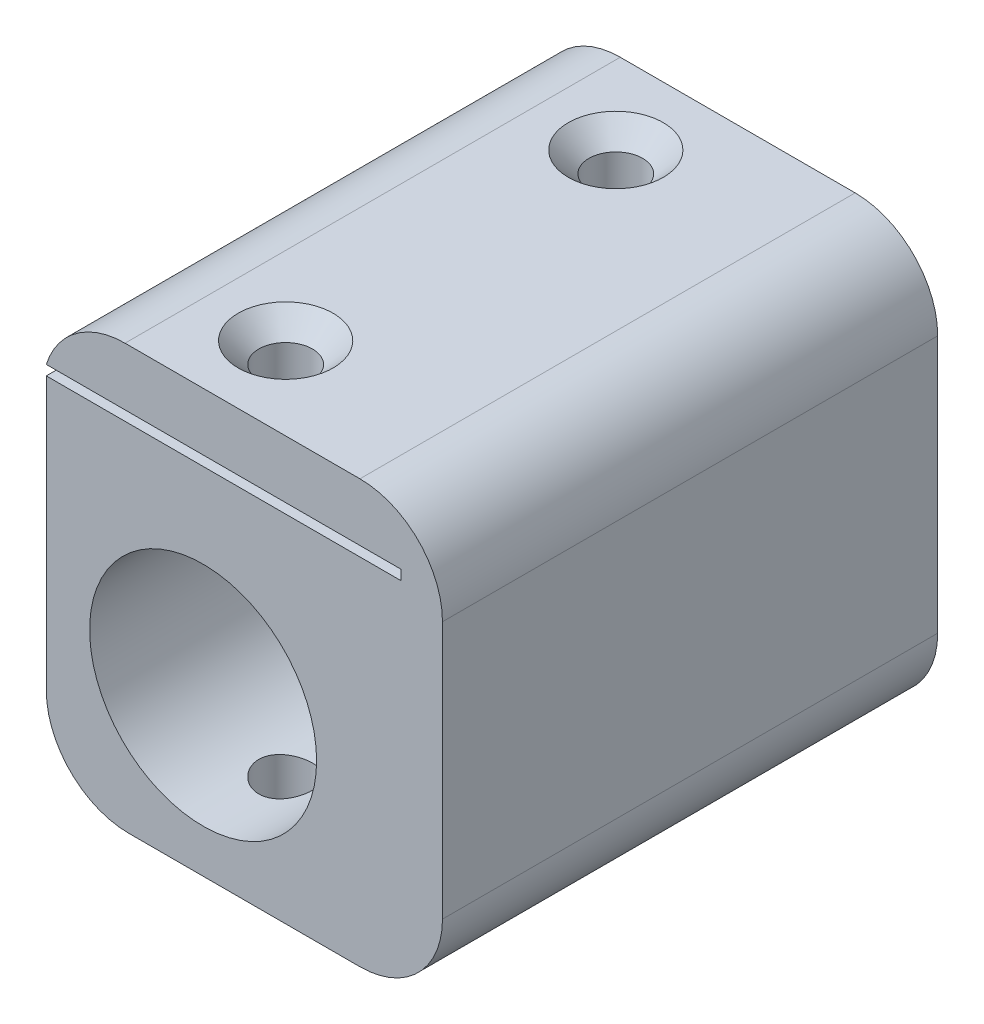
SolidWorks part; units mm, degrees
ref_plane "Front Plane" through (0, 0, 0) normal (0, 0, 1) x (1, 0, 0)
ref_plane "Top Plane" through (0, 0, 0) normal (0, 1, 0) x (1, 0, 0)
ref_plane "Right Plane" through (0, 0, 0) normal (1, 0, 0) x (0, 0, -1)
sketch "Sketch1" plane through (0, 0, 0) normal (0, 0, 1) x (1, 0, 0)
  line L1 (-19, -19) -> (24, -19)
  line L2 (-19, -19) -> (-19, 24)
  line L3 (-19, 24) -> (24, 24)
  line L4 (24, -19) -> (24, 24)
  line L7 (24, -19) -> (29, -19)
  line L8 (24, -19) -> (24, 32.2)
  line L9 (24, 32.2) -> (29, 32.2)
  line L10 (29, -19) -> (29, 32.2)
  line L11 (24, 32.2) -> (-19, 32.2)
  line L12 (24, 32.2) -> (24, 25.2)
  line L13 (24, 25.2) -> (-19, 25.2)
  line L14 (-19, 32.2) -> (-19, 25.2)
  circle A0 centre (0, 0) radius 13.75
  dimension "D1" = 27.5
  dimension "D7" = 19
  dimension "D3" = 19
  dimension "D8" = 24
  dimension "D2" = 1.2
  dimension "D4" = 24
  dimension "D5" = 5
  dimension "D6" = 7
extrude "Boss-Extrude1" add sketch "Sketch1" along normal blind 60 contours L1 L4 L3 L2 A0 | L11 L14 L13 L8 | L7 L10 L9 L8 L4 region at (-18.3919, 2.5, 0) region at (26.5, 6.6, 0) region at (2.5, 28.7, 0)
sketch "Sketch2" plane through (0, 0, 60) normal (0, 0, 1) x (1, 0, 0)
  line L0 (0, 0) -> (0, 32.2) construction
  line L1 (-19, 32.2) -> (29, 32.2) construction
sketch "Sketch3" plane through (0, 32.2, 0) normal (0, 1, 0) x (1, 0, 0)
  line L2 (-19, -30) -> (29, -30) construction
  line L3 (-19, -60) -> (-19, 0) construction
  line L4 (29, -60) -> (29, 0) construction
  circle A0 centre (0, -50) radius 3.25
  circle A1 centre (0, -10) radius 3.25
  dimension "D1" = 6.5
  dimension "D2" = 40
extrude "Cut-Extrude5" cut sketch "Sketch3" against normal through all
chamfer "Chamfer2" distance 2.5 angle 45 2 edges at (0, 32.2, 53.25) (0, 32.2, 6.75)
sketch "Sketch7" plane through (0, -19, 0) normal (0, -1, 0) x (1, 0, 0)
  line L0 (-19, 30) -> (29, 30) construction
  line L1 (0, 43.5337) -> (5.6, 46.7668)
  line L2 (5.6, 46.7668) -> (5.6, 53.2332)
  line L3 (5.6, 53.2332) -> (0, 56.4663)
  line L4 (0, 56.4663) -> (-5.6, 53.2332)
  line L5 (-5.6, 53.2332) -> (-5.6, 46.7668)
  line L6 (-5.6, 46.7668) -> (0, 43.5337)
  line L7 (-19, 60) -> (-19, 0) construction
  line L8 (29, 60) -> (29, 0) construction
  line L9 (-5.6, 13.2332) -> (0, 16.4663)
  line L10 (-5.6, 6.7668) -> (-5.6, 13.2332)
  line L11 (0, 3.5337) -> (-5.6, 6.7668)
  line L12 (5.6, 6.7668) -> (0, 3.5337)
  line L13 (5.6, 13.2332) -> (5.6, 6.7668)
  line L14 (0, 16.4663) -> (5.6, 13.2332)
  circle A0 centre (0, 50) radius 5.6 construction
  dimension "D1" = 11.2
extrude "Cut-Extrude6" cut sketch "Sketch7" along normal blind 15 from offset 38 offset against normal yes
fillet "Fillet1" radius 10 4 edges at (-19, 32.2, 30) (29, 32.2, 30) (29, -19, 30) (-19, -19, 30)
